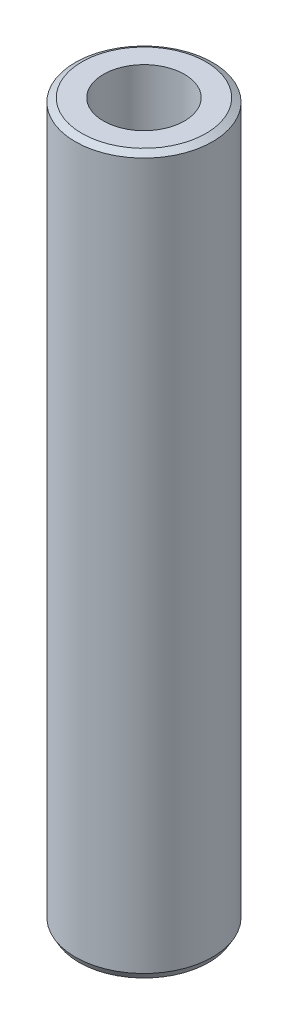
SolidWorks part; units mm, degrees
ref_plane "Front Plane" through (0, 0, 0) normal (0, 0, 1) x (1, 0, 0)
ref_plane "Top Plane" through (0, 0, 0) normal (0, 1, 0) x (1, 0, 0)
ref_plane "Right Plane" through (0, 0, 0) normal (1, 0, 0) x (0, 0, -1)
sketch "Sketch1" plane through (0, 0, 0) normal (0, 1, 0) x (1, 0, 0)
  circle A0 centre (0, 0) radius 57.5
  dimension "SHAFT_OD" = 115
extrude "Boss-Extrude1" add sketch "Sketch1" along normal blind 600
sketch "Sketch2" plane through (0, 0, 0) normal (0, 1, 0) x (1, 0, 0)
  circle A0 centre (0, 0) radius 33.9092
  dimension "BORE_D" = 67.8185
extrude "Cut-Extrude1" cut sketch "Sketch2" along normal through all
chamfer "Chamfer1" distance 3.2001 angle 60 2 edges at (0, 600, 57.5) (0, 0, 57.5) first distance on face at (0, 600, 57.5) first distance on face at (0, 0, 33.9092)
